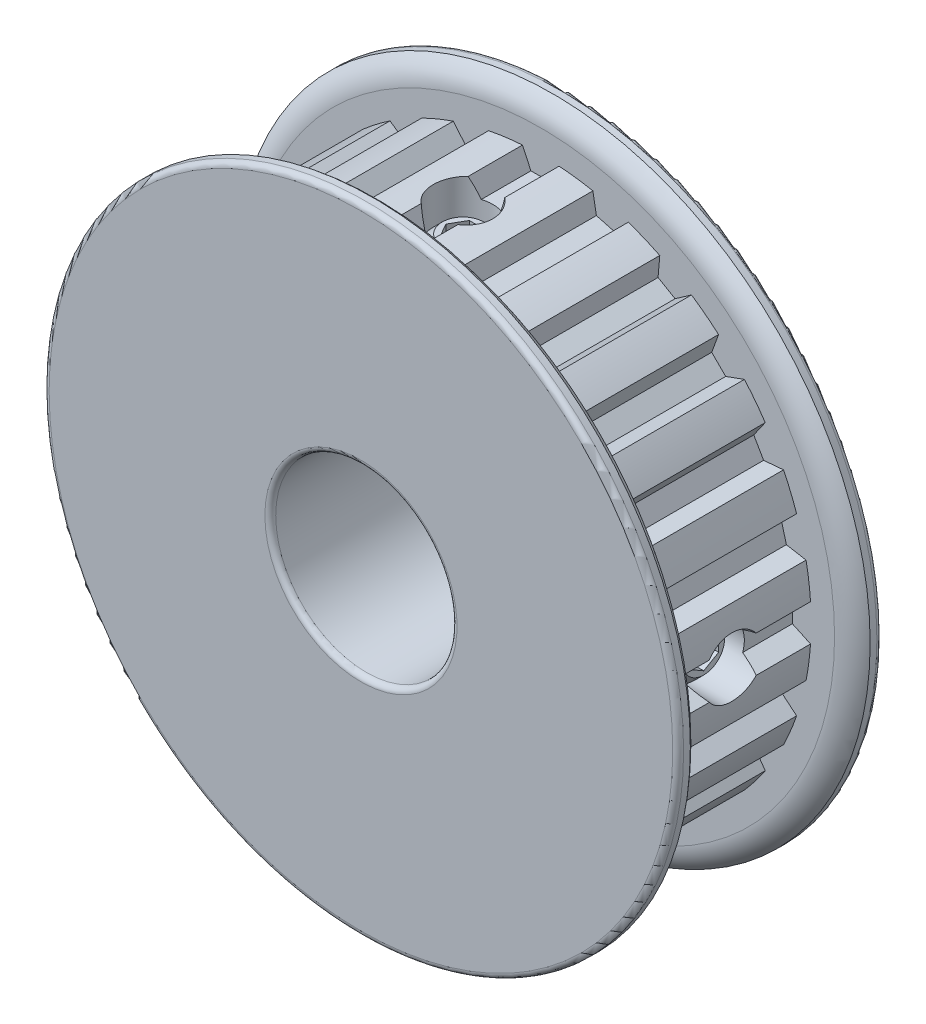
SolidWorks part; units mm, degrees
note: '?' marks a value the reader was unsure of.
ref_plane "Front Plane" through (0, 0, 0) normal (0, 0, 1) x (1, 0, 0)
ref_plane "Top Plane" through (0, 0, 0) normal (0, 1, 0) x (1, 0, 0)
ref_plane "Right Plane" through (0, 0, 0) normal (1, 0, 0) x (0, 0, -1)
sketch "Sketch1" plane through (0, 0, 0) normal (0, 0, 1) x (1, 0, 0)
  line L0 (-1.2827, 18.8976) -> (-0.6905, 17.6276)
  line L1 (-0.6905, 17.6276) -> (0.6905, 17.6276)
  line L2 (0.6905, 17.6276) -> (1.2827, 18.8976)
  line L3 (-1.2827, 18.8976) -> (1.2827, 18.8976)
  line L4 (0, 0) -> (0, 17.6276) construction
  line L5 (0, 17.6276) -> (0, 19.9136) construction
  circle A0 centre (0, 0) radius 19.4056 construction
  circle A1 centre (0, 0) radius 22.225 construction
  circle A2 centre (0, 0) radius 18.9411 construction
  point P6 (0, 18.8976)
  point P11 (0, 19.4056)
  point P13 (0, 22.225)
  point P14 (0, 18.9411)
  dimension "D1" = 1.016
  dimension "PD" = 38.8112
  dimension "D2" = 0.508
  dimension "OD" = 44.45
  dimension "b" = 50
  dimension "bt" = 2.5654
  dimension "ht" = 1.27
  dimension "hs" = 2.286
sketch "Sketch2" plane through (0, 0, 0) normal (1, 0, 0) x (0, 0, -1)
  line L0 (-7.1501, 6.35) -> (7.1501, 6.35)
  line L3 (-7.1501, 6.35) -> (-7.1501, 22.225)
  line L4 (-7.1501, 22.225) -> (-5.4483, 22.225) construction
  line L5 (-5.4483, 22.225) -> (-5.4483, 18.9411) construction
  line L6 (-5.4483, 18.9411) -> (5.4483, 18.9411)
  line L7 (5.4483, 18.9411) -> (5.4483, 22.225) construction
  line L8 (5.4483, 22.225) -> (7.1501, 22.225) construction
  line L9 (7.1501, 22.225) -> (7.1501, 6.35)
  line L10 (-7.1501, 0) -> (7.1501, 0) construction
  line L13 (-7.1501, 22.225) -> (-6.2992, 22.225)
  line L14 (-5.4483, 20.583) -> (-5.4483, 18.9411)
  line L15 (5.4483, 18.9411) -> (5.4483, 20.583)
  line L16 (6.2992, 22.225) -> (7.1501, 22.225)
  arc A0 (-5.4483, 20.583) -> (-6.2992, 22.225) centre (-7.458, 20.583) ccw
  arc A1 (5.4483, 20.583) -> (6.2992, 22.225) centre (7.458, 20.583) cw
  point P12 (-5.4483, 20.583)
  point P14 (-6.2992, 22.225)
  point P20 (5.4483, 20.583)
  point P21 (6.2992, 22.225)
  point P25 (5.4483, 0)
  point P26 (-5.4483, 0)
  dimension "OA" = 14.3002
  dimension "Bore" = 12.7
  dimension "Outside Width" = 14.3002
  dimension "Inside Width" = 10.8966
revolve "Revolve1" add sketch "Sketch2" angle 360 mid plane about L10
sketch "Sketch3" plane through (0, 0, 0) normal (0, 0, 1) x (1, 0, 0)
  line L0 (-0.6905, 17.6276) -> (0.6905, 17.6276) construction
  line L1 (0.6905, 17.6276) -> (1.2827, 18.8976) construction
  line L2 (-1.2827, 18.8976) -> (-0.6905, 17.6276) construction
  line L3 (-0.6905, 17.6276) -> (0.6905, 17.6276)
  line L4 (0.6905, 17.6276) -> (1.2827, 18.8976)
  line L5 (-1.2827, 18.8976) -> (-0.6905, 17.6276)
  circle A0 centre (0, 0) radius 18.9411 construction
  arc A1 (1.2827, 18.8976) -> (-1.2827, 18.8976) centre (0, 0) ccw
extrude "Cut-Extrude1" cut sketch "Sketch3" against normal up to vertex (5.4483 mm away) from vertex at 5.4483 starting at point (0, 18.9411, 5.4483)
pattern_circular "CirPattern1" count 24 over 360 about axis through (0, 0, 0) along (0, 0, 1) of "Cut-Extrude1"
fillet "Fillet1" radius 0.381 4 edges at (6.35, 0, -7.1501) (22.225, 0, -7.1501) (22.225, 0, 7.1501) (6.35, 0, 7.1501)
sketch "Sketch5" plane through (0, 0, 0) normal (0, 1, 0) x (1, 0, 0)
  line L1 (1.2827, 0) -> (-1.2827, 0) construction
  line L2 (1.2827, 5.4483) -> (1.2827, -5.4483) construction
  line L3 (-1.2827, 5.4483) -> (-1.2827, -5.4483) construction
  circle A0 centre (0, 0) radius 2.0828
extrude "Cut-Extrude2" cut sketch "Sketch5" along normal through all
sketch "Sketch6" plane through (0, 0, 0) normal (1, 0, 0) x (0, 0, -1)
  line L0 (0, 16.8656) -> (0, 7.112)
  line L1 (6.7691, 6.35) -> (-6.7691, 6.35) construction
  line L3 (2.0828, 17.6276) -> (-2.0828, 17.6276) construction
  line L4 (-1.965, 17.6276) -> (-2.0828, 17.6276) construction
  line L5 (2.0828, 17.6276) -> (1.965, 17.6276) construction
  line L6 (0, 16.8656) -> (-1.458, 16.8656)
  line L7 (-1.458, 16.8656) -> (-2.0828, 16.2408)
  line L8 (-2.0828, 16.2408) -> (-2.0828, 7.7368)
  line L9 (-2.0828, 7.7368) -> (-1.458, 7.112)
  line L10 (-1.458, 7.112) -> (0, 7.112)
  point P12 (0, 6.35)
  point P19 (0, 17.6276)
  dimension "D1" = 0.762
  dimension "D2" = 0.762
  dimension "D3" = 135
  dimension "D4" = 0.6248
revolve "Revolve2" add sketch "Sketch6" angle 360 about L0
sketch "Sketch7" plane through (0, 16.8656, 0) normal (0, 1, 0) x (1, 0, 0)
  line L1 (1.2025, 0) -> (0.6013, 1.0414)
  line L2 (0.6013, 1.0414) -> (-0.6013, 1.0414)
  line L3 (-0.6013, 1.0414) -> (-1.2025, 0)
  line L4 (-1.2025, 0) -> (-0.6013, -1.0414)
  line L5 (-0.6013, -1.0414) -> (0.6013, -1.0414)
  line L6 (0.6013, -1.0414) -> (1.2025, 0)
  circle A0 centre (0, 0) radius 1.0414 construction
  dimension "D1" = 2.0828
extrude "Cut-Extrude3" cut sketch "Sketch7" against normal blind 1.0414
pattern_circular "CirPattern2" count 2 over 270 about axis through (0, 0, 0) along (0, 0, 1) of "Cut-Extrude2", "Revolve2", "Cut-Extrude3"
ref_axis "Center Axis 1" through (0, 0, -6.7691) along (0, 0, 1)?
ref_plane "Contact Plane 1" through (0, 0, 7.1501) normal (0, 0, 1) x (1, 0, 0)
ref_plane "Contact Plane 2" through (0, 0, -7.1501) normal (0, 0, -1) x (-1, 0, 0)
equation "\"D4@Sketch6\" = \"Set Screw Dia@Sketch5\" * .15"
equation "\"D1@Sketch7\" = \"Set Screw Dia@Sketch5\" / 2"
equation "\"D1@Cut-Extrude3\" = \"Set Screw Dia@Sketch5\" / 4"
